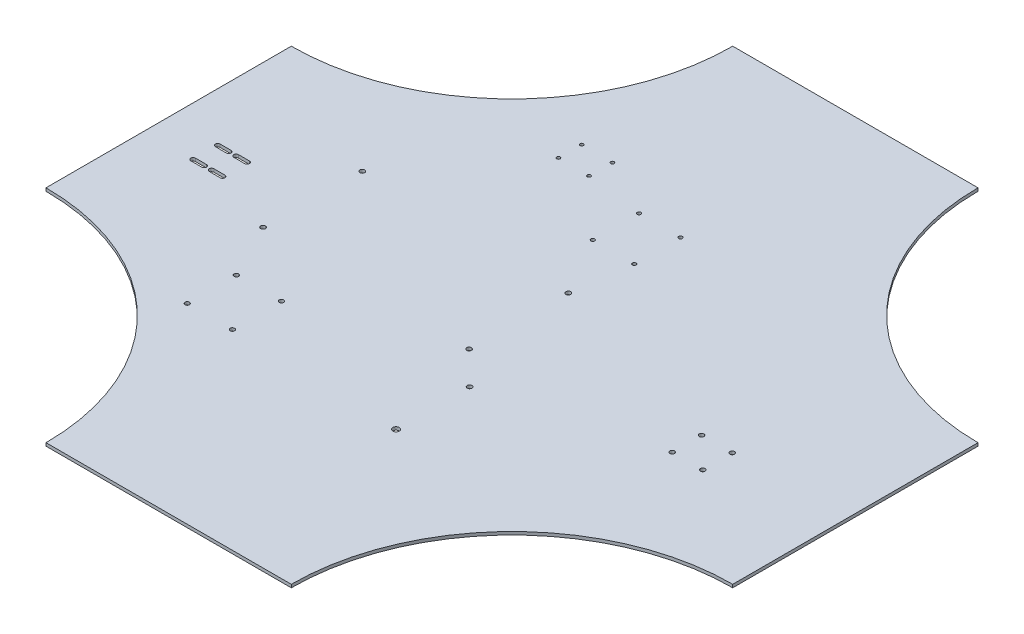
SolidWorks part; units mm, degrees
material "6061 Alloy"
ref_plane "Front Plane" through (0, 0, 0) normal (0, 0, 1) x (1, 0, 0)
ref_plane "Top Plane" through (0, 0, 0) normal (0, 1, 0) x (1, 0, 0)
ref_plane "Right Plane" through (0, 0, 0) normal (1, 0, 0) x (0, 0, -1)
sketch "Sketch1" plane through (0, 0, 0) normal (0, 1, 0) x (1, 0, 0)
  line L9 (-127, -355.6) -> (127, -355.6)
  line L10 (-355.6, -127) -> (-355.6, 127)
  line L11 (-127, 355.6) -> (127, 355.6)
  line L12 (355.6, -127) -> (355.6, 127)
  line L13 (-193.9554, -193.9554) -> (193.9554, 193.9554) construction
  line L14 (-193.9554, 193.9554) -> (193.9554, -193.9554) construction
  arc A8 (-355.6, 127) -> (-127, 355.6) centre (-355.6, 355.6) ccw
  arc A9 (127, 355.6) -> (355.6, 127) centre (355.6, 355.6) ccw
  arc A10 (355.6, -127) -> (127, -355.6) centre (355.6, -355.6) ccw
  arc A11 (-127, -355.6) -> (-355.6, -127) centre (-355.6, -355.6) ccw
  point P0 (0, 0)
  point P1 (0, 0)
  point P2 (0, 0)
  dimension "D3" = 457.2
  dimension "D4" = 457.2
  dimension "D5" = 457.2
  dimension "D6" = 457.2
  dimension "D1" = 711.2
  dimension "D2" = 711.2
extrude "Boss-Extrude1" add sketch "Sketch1" along normal blind 3.175
sketch "Sketch2" plane through (0, 3.175, 0) normal (0, 1, 0) x (1, 0, 0)
  line L0 (-304.8, 2.413) -> (-293.37, 2.413)
  line L1 (-304.8, -22.987) -> (-293.37, -22.987)
  line L2 (-293.37, -2.413) -> (-304.8, -2.413)
  line L3 (-285.75, -2.413) -> (-274.32, -2.413)
  line L4 (-285.75, -22.987) -> (-274.32, -22.987)
  line L5 (-274.32, 2.413) -> (-285.75, 2.413)
  line L6 (-293.37, -27.813) -> (-304.8, -27.813)
  line L7 (-355.6, 127) -> (-355.6, -127) construction
  line L8 (-274.32, -27.813) -> (-285.75, -27.813)
  arc A0 (-293.37, -2.413) -> (-293.37, 2.413) centre (-293.37, 0) ccw
  arc A1 (-274.32, -2.413) -> (-274.32, 2.413) centre (-274.32, 0) ccw
  arc A2 (-274.32, -27.813) -> (-274.32, -22.987) centre (-274.32, -25.4) ccw
  arc A3 (-293.37, -27.813) -> (-293.37, -22.987) centre (-293.37, -25.4) ccw
  arc A4 (-285.75, 2.413) -> (-285.75, -2.413) centre (-285.75, 0) ccw
  arc A5 (-304.8, 2.413) -> (-304.8, -2.413) centre (-304.8, 0) ccw
  arc A6 (-304.8, -22.987) -> (-304.8, -27.813) centre (-304.8, -25.4) ccw
  arc A7 (-285.75, -22.987) -> (-285.75, -27.813) centre (-285.75, -25.4) ccw
  dimension "D1" = 4.826
  dimension "D2" = 4.826
  dimension "D3" = 4.826
  dimension "D4" = 4.826
  dimension "D5" = 4.826
  dimension "D6" = 4.826
  dimension "D7" = 4.826
  dimension "D8" = 4.826
  dimension "D9" = 11.43
  dimension "D10" = 11.43
  dimension "D11" = 11.43
  dimension "D12" = 11.43
  dimension "D13" = 19.05
  dimension "D14" = 19.05
  dimension "D15" = 25.4
  dimension "D16" = 25.4
  dimension "D17" = 0
  dimension "D18" = 50.8
extrude "Cut-Extrude1" cut sketch "Sketch2" against normal through all both and the other way through all
sketch "Sketch4" plane through (0, 3.175, 0) normal (0, 1, 0) x (1, 0, 0)
  circle A0 centre (237.49, -9.4302) radius 2.413
  circle A1 centre (205.74, -9.4302) radius 2.413
  circle A2 centre (237.49, -39.9102) radius 2.413
  circle A3 centre (205.74, -39.9102) radius 2.413
extrude "Cut-Extrude2" cut sketch "Sketch4" against normal through all
sketch "Sketch5" plane through (0, 0, 0) normal (0, -1, 0) x (1, 0, 0)
  circle A0 centre (-207.7901, 50.0166) radius 2.5
  circle A1 centre (-206.624, -51.5767) radius 2.5
  circle A2 centre (8.0956, 52.4945) radius 2.478
  circle A3 centre (9.2617, -49.0988) radius 2.5
extrude "Cut-Extrude3" cut sketch "Sketch5" against normal through all
sketch "Sketch6" plane through (0, 0, 0) normal (0, -1, 0) x (1, 0, 0)
  circle A0 centre (-131.9657, 157.5947) radius 2.3218
  circle A1 centre (-131.9657, 106.7947) radius 2.3218
  circle A2 centre (-178.7006, 106.7947) radius 2.3218
  circle A3 centre (-178.7006, 157.5947) radius 2.3218
  circle A4 centre (42.2659, 162.3375) radius 3.343
  circle A5 centre (42.2659, 86.1375) radius 2.5
  circle A6 centre (17.3717, -109.2657) radius 1.905
  circle A7 centre (-25.6811, -109.3842) radius 1.905
  circle A8 centre (-25.5498, -157.136) radius 1.905
  circle A9 centre (17.503, -157.0152) radius 1.905
  circle A10 centre (-84.8824, -188.8713) radius 1.75
  circle A11 centre (-85.0918, -164.8722) radius 1.75
  circle A12 centre (-116.8812, -189.1505) radius 1.75
  circle A13 centre (-117.0906, -165.1514) radius 1.75
extrude "Cut-Extrude4" cut sketch "Sketch6" against normal through all
